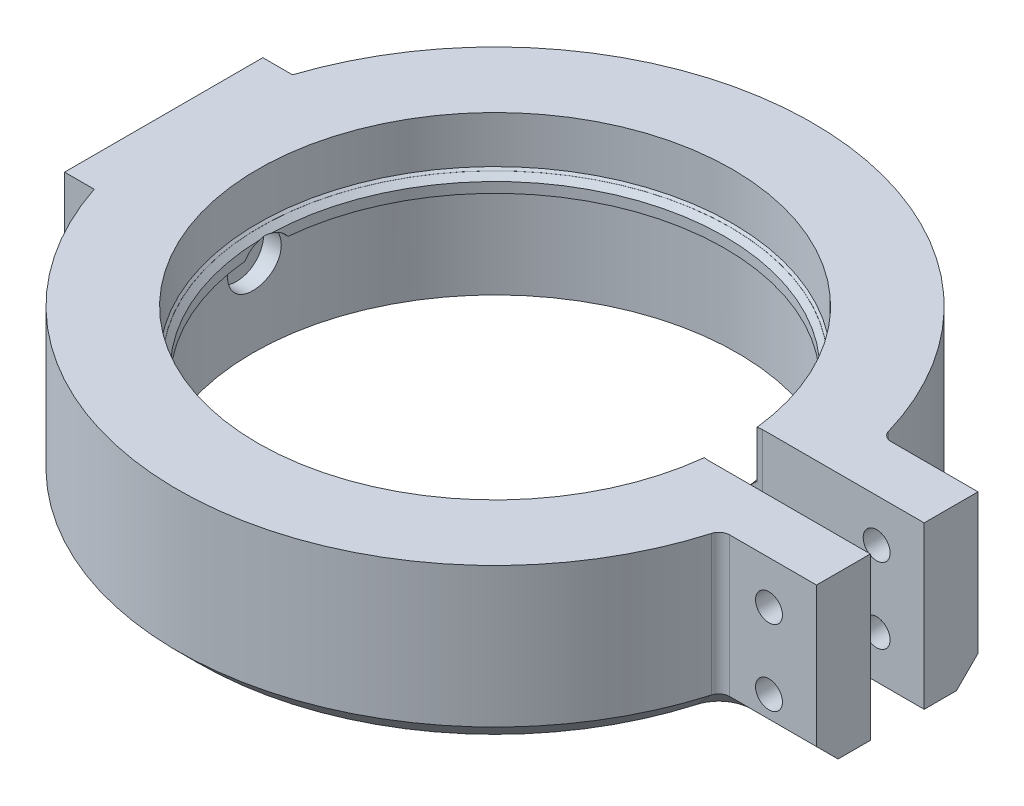
SolidWorks part; units mm, degrees
ref_plane "Front Plane" through (0, 0, 0) normal (0, 0, 1) x (1, 0, 0)
ref_plane "Top Plane" through (0, 0, 0) normal (0, 1, 0) x (1, 0, 0)
ref_plane "Right Plane" through (0, 0, 0) normal (1, 0, 0) x (0, 0, -1)
sketch "Sketch3" plane through (0, 0, 0) normal (0, 1, 0) x (1, 0, 0)
  line L2 (22.3607, 2.5) -> (37.3607, 2.5)
  line L4 (-28.0259, 9.2086) -> (-30.7819, 9.2086)
  line L5 (28.5307, 7.5) -> (37.3607, 7.5)
  line L6 (37.3607, 2.5) -> (37.3607, 7.5)
  line L7 (22.3607, -2.5) -> (37.3607, -2.5)
  line L9 (28.5307, -7.5) -> (37.3607, -7.5)
  line L10 (37.3607, -2.5) -> (37.3607, -7.5)
  line L11 (-28.0259, -9.2086) -> (-30.7819, -9.2086)
  line L12 (-30.7819, 9.2086) -> (-30.7819, -9.2086)
  arc A0 (22.3607, 2.5) -> (22.3607, -2.5) centre (0, 0) ccw
  arc A1 (28.5307, 7.5) -> (-28.0259, 9.2086) centre (0, 0) ccw
  arc A2 (-28.0259, -9.2086) -> (28.5307, -7.5) centre (0, 0) ccw
  point P4 (25.2637, 0)
  point P9 (-27.5345, 0)
  dimension "D1" = 45
  dimension "D2" = 7
  dimension "D4" = 0
  dimension "D6" = 5
  dimension "D7" = 5
extrude "Boss-Extrude1" add sketch "Sketch3" along normal blind 15
sketch "Sketch5" plane through (0, 0, 0) normal (0, 1, 0) x (1, 0, 0)
  point P0 (0, 0)
sketch "Sketch6" plane through (0, 0, 0) normal (0, 0, 1) x (1, 0, 0)
  line L0 (0, 0) -> (0, 18.5471) construction
ref_plane "Plane1" through (0, 0, 0) normal (-0.1111, 0, -0.9938) x (-0.9938, 0, 0.1111)
sketch "Sketch8" plane through (0, 0, 0) normal (-0.1111, 0, -0.9938) x (-0.9938, 0, 0.1111)
  line L0 (-22.5, 9) -> (-21.33, 9)
  line L2 (-21.33, 9) -> (-21.33, 10.45)
  line L3 (-21.33, 10.45) -> (-22.04, 10.45)
  line L4 (-22.04, 10.45) -> (-22.04, 15)
  line L5 (-22.04, 15) -> (-22.5, 15)
  line L6 (-22.5, 15) -> (-22.5, 9)
  dimension "D1" = 6
  dimension "D2" = 1.45
  dimension "D3" = 0.46
revolve "Revolve2" add sketch "Sketch8" angle 347.2 about L0
sketch "Sketch9" plane through (0, 0, 7.5) normal (0, 0, 1) x (1, 0, 0)
  line L0 (28.5307, 15) -> (37.3607, 15) construction
  line L1 (28.5307, 0) -> (37.3607, 0) construction
  circle A0 centre (32.9457, 11) radius 1.25
  circle A1 centre (32.9457, 4) radius 1.25
  dimension "D1" = 2.5
  dimension "D2" = 2.5
  dimension "D3" = 4
  dimension "D4" = 4
extrude "Cut-Extrude1" cut sketch "Sketch9" against normal blind 20
sketch "Sketch10" plane through (-30.7819, 0, 0) normal (-1, 0, 0) x (0, 0, 1)
  line L0 (0, 0) -> (0, 18.5471) construction
  circle A0 centre (0, 7.5) radius 2.475
  dimension "D1" = 4.95
extrude "Cut-Extrude3" cut sketch "Sketch10" against normal blind 4
sketch "Sketch12" plane through (-26.7819, 0, 0) normal (-1, 0, 0) x (0, 0, 1)
  circle A0 centre (0, 7.5) radius 1
  dimension "D1" = 2
extrude "Cut-Extrude4" cut sketch "Sketch12" against normal blind 5
sketch "Sketch13" plane through (0, 0, 0) normal (1, 0, 0) x (0, 0, -1)
  circle A0 centre (0, 7.5) radius 2.5
  dimension "D1" = 5
extrude "Cut-Extrude6" cut sketch "Sketch13" against normal blind 24
chamfer "Chamfer1" distance 0.2 angle 45 2 edges at (-0.2594, 9, 22.4985) (-22.04, 10.45, -0.0079)
fillet "Fillet1" radius 1 2 edges at (28.5307, 7.5, -7.5) (28.5307, 7.5, 7.5)
chamfer "Chamfer2" distance 0.5 angle 45 1 edges at (-21.33, 10.45, -0.0077)
chamfer "Chamfer3" distance 2 angle 45 6 edges at (33.3262, 0, -7.5) (28.6911, 0, -7.7004) (0.5167, 0, -29.4955) (33.3262, 0, 7.5) (28.6911, 0, 7.7004) (0.5167, 0, 29.4955)
